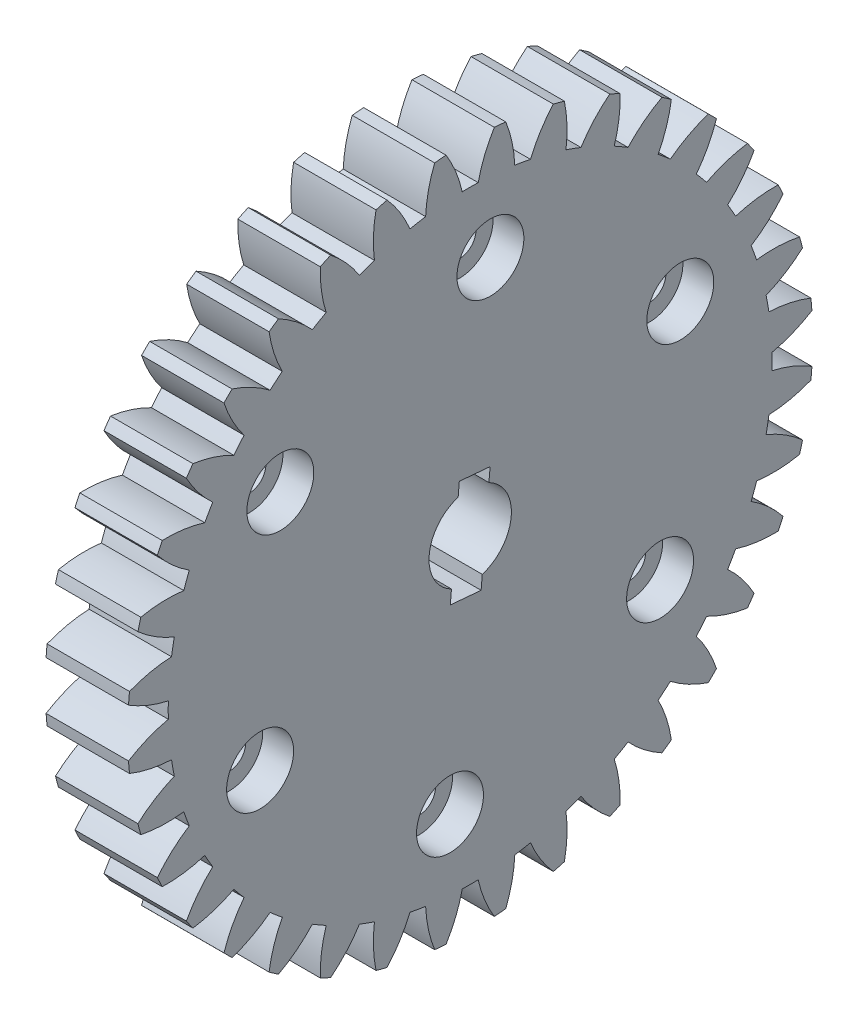
SolidWorks part; units mm, degrees
material "PLA personnalisé"
ref_plane "Plane1" through (0, 0, 0) normal (0, 0, 1) x (1, 0, 0)
ref_plane "Plane2" through (0, 0, 0) normal (0, 1, 0) x (1, 0, 0)
ref_plane "Plane3" through (0, 0, 0) normal (1, 0, 0) x (0, 0, -1)
other "Configuration Table"
sketch "HoldingSke" plane through (0, 0, 0) normal (0, 1, 0) x (1, 0, 0)
  line L0 (0, 0) -> (0.4623, -0.3359)
  line L1 (-15, 0) -> (100, 0) construction
  line L2 (0, 0) -> (-2.1039, 2.3779)
  line L3 (0, 0) -> (-11.863, 4.5341)
  line L4 (0, 0) -> (6.9867, 5.0761)
  line L5 (0, 0) -> (-46.8476, -17.4728)
  line L6 (0, 0) -> (-6.6317, -4.4744)
  line L7 (-2.1039, 2.3779) -> (8.6586, 51.2059)
  line L8 (-76.2, 54.61) -> (-74.8, 54.61)
  line L9 (-71.009, 38.7566) -> (-53.1078, 45.2721)
  line L10 (-76.2, 71.12) -> (104.1128, 71.12)
  line L11 (0, 0) -> (-8, 0)
  line L12 (-76.2, 101.6) -> (-76.147, 101.6)
  line L13 (24.9733, 27.94) -> (52.9518, 28.4284)
  line L14 (24.9733, 27.94) -> (24.9743, 27.94)
  line L15 (24.9733, 27.94) -> (100.4006, 29.5858)
  line L16 (-63.627, -1.75) -> (-12.827, -1.75)
  circle A0 centre (0, 0) radius 4
  circle A1 centre (0, 0) radius 29.3115
  circle A2 centre (0, 0) radius 37.5
  circle A3 centre (0, 0) radius 4
  dimension "MHD" = 58.623
  dimension "Hub_dia" = 75
  dimension "Bore" = 8
  dimension "MBD" = 8
  dimension "Num_teeth" = 36
  dimension "Pitch" = 0.5714
  dimension "Overall_len" = 50
  dimension "Show_teeth" = 36
  dimension "Thickness" = 8
  dimension "OAL" = 50.0001
  dimension "T_dim" = 1.4
  dimension "Ap" = 20
  dimension "H" = 19.05
  dimension "Pitch_radius" = 180.3128
  dimension "Width" = 8
  dimension "Backlash" = 0.053
  dimension "Addendum_fac" = 1
  dimension "Dedendum_fac" = 1.25
  dimension "Clearance_fac" = 0.25
  dimension "Dedendum_add" = 0.001
  dimension "Module" = 1.75
sketch "BasProSke" plane through (0, 0, 0) normal (0, 1, 0) x (1, 0, 0)
  line L0 (-10, 0) -> (60, 0) construction
  line L1 (0, 0) -> (0, 33.25)
  line L2 (0, 0) -> (8, 0)
  line L3 (8, 0) -> (8, 33.25)
  line L4 (8, 33.25) -> (0, 33.25)
  dimension "Thickness" = 8
  dimension "Diameter" = 66.5
revolve "Base-Revolve" add sketch "BasProSke" angle 360 about L0
sketch "TooCutSke" plane through (0, 0, 0) normal (1, 0, 0) x (0, 0, -1)
  line L1 (0, 0) -> (0, 107) construction
  line L2 (0, 0) -> (-1.4667, 31.4658) construction
  line L3 (0, 0) -> (-5.4863, 62.7083) construction
  line L4 (-1.4667, 31.4658) -> (-2.7431, 31.3542) construction
  arc A0 (0.7738, 29.3013) -> (-0.7738, 29.3013) centre (0, 0) ccw
  arc A1 (2.3593, 33.1917) -> (-2.3593, 33.1917) centre (0, 0) ccw
  circle A2 centre (0, 0) radius 31.5 construction
  circle A3 centre (0, 0) radius 29.6003 construction
  arc A4 (-0.7738, 29.3013) -> (-2.3593, 33.1917) centre (-13.0715, 26.5578) ccw
  arc A5 (2.3593, 33.1917) -> (0.7738, 29.3013) centre (13.0715, 26.5578) ccw
  dimension "Root_dia" = 58.623
  dimension "Overcut_dia" = 66.5508
  dimension "Pitch_dia" = 63
  dimension "Base_dia" = 59.2006
  dimension "Flank_rad" = 12.6
  dimension "Half_ang" = 5
  dimension "Half_CT" = 1.2813
extrude "ToothCut" cut sketch "TooCutSke" along normal through all
fillet "Breaks" [suppressed] radius 0.035 tangent propagation no
fillet "RootFillets" [suppressed] radius 0.4385
pattern_circular "TeethCuts" count 36 every 10 about axis through (-10, 0, 0) along (1, 0, 0) of "ToothCut", "RootFillets", "Breaks"
sketch "HubNeaOneSke" plane through (0, 0, 0) normal (-1, 0, 0) x (0, 0, 1)
  circle A0 centre (0, 0) radius 29.3115
  dimension "Diameter" = 58.623
extrude "HubNearOne" [suppressed] add sketch "HubNeaOneSke" along normal blind 42.0001
sketch "HubNeaBotSke" plane through (0, 0, 0) normal (-1, 0, 0) x (0, 0, 1)
  circle A0 centre (0, 0) radius 29.3115
  dimension "Diameter" = 58.623
extrude "HubNearBoth" [suppressed] add sketch "HubNeaBotSke" along normal blind 21
ref_plane "FarPln" through (8, 0, 0) normal (1, 0, 0) x (0, 0, -1)
sketch "HubFarSke" plane through (8, 0, 0) normal (1, 0, 0) x (0, 0, -1)
  circle A0 centre (0, 0) radius 29.3115
  dimension "Diameter" = 58.623
extrude "HubFar" [suppressed] add sketch "HubFarSke" along normal blind 21
sketch "BorSke" plane through (0, 0, 0) normal (1, 0, 0) x (0, 0, -1)
  circle A0 centre (0, 0) radius 4
  dimension "Diameter" = 8
extrude "Bore" cut sketch "BorSke" along normal mid plane 100.0001
sketch "KeySke" plane through (0, 0, 0) normal (1, 0, 0) x (0, 0, -1)
  line L0 (-1.5, 0) -> (-1.5, 5.4)
  line L1 (-1.5, 5.4) -> (1.5, 5.4)
  line L2 (1.5, 5.4) -> (1.5, 0)
  line L3 (0, 0) -> (0, 34) construction
  line L4 (-1.5, 0) -> (1.5, 0)
  dimension "Offset" = 5.4
  dimension "Width" = 3
extrude "Keyway" [suppressed] cut sketch "KeySke" along normal mid plane 100.0001
pattern_circular "Keyway2" [suppressed] count 2 every 90 about axis through (-10, 0, 0) along (1, 0, 0) reverse direction yes
sketch "Esquisse2" plane through (8, 0, 0) normal (1, 0, 0) x (0, 0, -1)
  line L0 (2.8979, 33.1235) -> (0, 0) construction
  line L1 (1.3673, 15.6288) -> (2.5547, 29.2)
  arc A0 (3.4508, 33.0704) -> (2.3442, 33.1673) centre (0, 0) ccw construction
  circle A1 centre (0, 0) radius 29.3115
  circle A2 centre (0, 0) radius 15.6885
  circle A3 centre (1.961, 22.4144) radius 1.6
  circle A4 centre (0, 0) radius 22.5
  dimension "D1" = 3.2
  dimension "D2" = 45
extrude "Enlèv. mat.-Extru.2" cut sketch "Esquisse2" against normal blind 10 contours A3
sketch "Esquisse3" plane through (8, 0, 0) normal (1, 0, 0) x (0, 0, -1)
  circle A0 centre (1.961, 22.4144) radius 3.25
  dimension "D1" = 6.5
extrude "Enlèv. mat.-Extru.3" cut sketch "Esquisse3" against normal blind 3
pattern_circular "Répétition circulaire1" count 6 over 360 about axis through (50.0001, 0, 0) along (-1, 0, 0) of "Enlèv. mat.-Extru.2", "Enlèv. mat.-Extru.3"
sketch "Esquisse4" plane through (8, 0, 0) normal (1, 0, 0) x (0, 0, -1)
  line L0 (0, 0) -> (1.961, 22.4144) construction
  line L1 (1.0585, -5.1117) -> (-1.9301, -4.8502)
  line L2 (1.0585, -5.1117) -> (1.9301, 4.8502)
  line L3 (1.9301, 4.8502) -> (-1.0585, 5.1117)
  line L4 (-1.9301, -4.8502) -> (-1.0585, 5.1117)
  line L5 (1.0585, -5.1117) -> (-1.0585, 5.1117) construction
  line L6 (1.9301, 4.8502) -> (-1.9301, -4.8502) construction
  point P0 (0, 0)
  dimension "D1" = 10
  dimension "D2" = 3
extrude "Enlèv. mat.-Extru.4" cut sketch "Esquisse4" against normal blind 10
equation "' \"Module@HoldingSke\" = 6.35"
equation "' \"Num_teeth@HoldingSke\" = 12"
equation "' \"Ap@HoldingSke\" =  20"
equation "' \"Ap@HoldingSke\" = 20"
equation "' \"Width@HoldingSke\" = 0.5 * 25.4"
equation "' \"Hub_dia@HoldingSke\"= 1 * 25.4"
equation "' \"Hub_dia@HoldingSke\" = 1 * 25.4"
equation "' \"Overall_len@HoldingSke\" = 1.0 * 25.4"
equation "' \"Bore@HoldingSke\" = 0.75 * 25.4"
equation "' \"T_dim@HoldingSke\" = 0.1 * 25.4"
equation "' \"Width@KeySke\" = 0.25 * 25.4"
equation "' \"Show_teeth@HoldingSke\" = 13"
equation "' \"Backlash@HoldingSke\" = 0.009 * 25.4"
equation "' \"Addendum_fac@HoldingSke\" = 1.0"
equation "' \"Dedendum_fac@HoldingSke\" = 1.25"
equation "' \"Dedendum_add@HoldingSke\" = 0.00005 * 25.4"
equation "' \"Clearance_fac@HoldingSke\" = 0.25"
equation "\"Pitch@HoldingSke\" = 1 / \"Module@HoldingSke\""
equation "\"Overcut_dia@TooCutSke\" = (\"Num_teeth@HoldingSke\" + 2 * \"Addendum_fac@HoldingSke\") / \"Pitch@HoldingSke\" + 0.002 * 25.4"
equation "\"Pitch_dia@TooCutSke\" = \"Num_teeth@HoldingSke\" / \"Pitch@HoldingSke\""
equation "\"Base_dia@TooCutSke\" = \"Num_teeth@HoldingSke\" / \"Pitch@HoldingSke\" * cos((\"Ap@HoldingSke\"  * 3.14159265 / 180))"
equation "\"Root_dia@TooCutSke\" = (\"Num_teeth@HoldingSke\" + 2) / \"Pitch@HoldingSke\" - 2 * (\"Addendum_fac@HoldingSke\" + \"Dedendum_fac@HoldingSke\") / \"Pitch@HoldingSke\" - \"Dedendum_add@HoldingSke\" * 2"
equation "\"Half_ang@TooCutSke\" = 180 / \"Num_teeth@HoldingSke\""
equation "\"Half_CT@TooCutSke\" = \"Num_teeth@HoldingSke\" / \"Pitch@HoldingSke\" * sin((3.14159265 / 2 / \"Num_teeth@HoldingSke\")) / 2 - 7 * \"Backlash@HoldingSke\" / 4"
equation "\"Flank_rad@TooCutSke\" = \"Num_teeth@HoldingSke\" / \"Pitch@HoldingSke\" / 5"
equation "\"Radius@RootFillets\" = \"Clearance_fac@HoldingSke\" / \"Pitch@HoldingSke\" + \"Dedendum_add@HoldingSke\""
equation "\"Break_rad@Breaks\" = 0.02 / \"Pitch@HoldingSke\""
equation "\"Thickness@HoldingSke\" = \"Width@HoldingSke\""
equation "\"OAL@HoldingSke\" = \"Thickness@HoldingSke\""
equation "\"MHD@HoldingSke\" = (\"Num_teeth@HoldingSke\" + 2) / \"Pitch@HoldingSke\" - 2 * (\"Addendum_fac@HoldingSke\" + \"Dedendum_fac@HoldingSke\")  / \"Pitch@HoldingSke\" - \"Dedendum_add@HoldingSke\" * 2"
equation "\"MBD@HoldingSke\" = (\"Num_teeth@HoldingSke\" + 2) / \"Pitch@HoldingSke\" - 2 * (\"Addendum_fac@HoldingSke\" + \"Dedendum_fac@HoldingSke\")  / \"Pitch@HoldingSke\" - \"Dedendum_add@HoldingSke\" * 2 - 0.002 * 25.4"
equation "\"MHD@HoldingSke\" = ((sgn( \"MHD@HoldingSke\" - \"Hub_dia@HoldingSke\" )-1)*( \"MHD@HoldingSke\" - \"Hub_dia@HoldingSke\" ))/-2+ \"Hub_dia@HoldingSke\""
equation "\"MBD@HoldingSke\" = ((sgn( \"MBD@HoldingSke\" - \"Bore@HoldingSke\" )-1)*( \"MBD@HoldingSke\" - \"Bore@HoldingSke\" ))/-2+ \"Bore@HoldingSke\""
equation "\"OAL@HoldingSke\" = ((sgn( \"OAL@HoldingSke\" - \"Overall_len@HoldingSke\" )+1)*( \"OAL@HoldingSke\" - \"Overall_len@HoldingSke\" ))/2 + \"Overall_len@HoldingSke\" + 0.000002 * 25.4"
equation "\"Num_teeth@TeethCuts\" = int( \"Show_teeth@HoldingSke\" ) + 1"
equation "\"Num_teeth@TeethCuts\" = ((sgn( \"Num_teeth@TeethCuts\" - \"Num_teeth@HoldingSke\" )-1)*( \"Num_teeth@TeethCuts\" - \"Num_teeth@HoldingSke\" ))/-2+ \"Num_teeth@HoldingSke\""
equation "\"Num_teeth@TeethCuts\" = ((sgn( \"Num_teeth@TeethCuts\" - 2.0)+1)*( \"Num_teeth@TeethCuts\" - 2.0))/2 +2.0"
equation "\"Angle@TeethCuts\" = 360.0 / \"Num_teeth@HoldingSke\""
equation "\"Diameter@BasProSke\" = (\"Num_teeth@HoldingSke\" + 2 * \"Addendum_fac@HoldingSke\") / \"Pitch@HoldingSke\""
equation "\"Thickness@BasProSke\"  = \"Thickness@HoldingSke\""
equation "' \"Fillet_rad@BasProSke\" =  \"Thickness@HoldingSke\" * 0.05"
equation "' \"Fillet_rad@BasProSke\" = \"Thickness@HoldingSke\" * 0.05"
equation "\"MHD@HoldingSke\" = ((sgn( \"MHD@HoldingSke\" - \"Root_dia@TooCutSke\" )-1)*( \"MHD@HoldingSke\" - \"Root_dia@TooCutSke\" ))/-2+ \"Root_dia@TooCutSke\""
equation "\"Diameter@HubNeaOneSke\" = \"MHD@HoldingSke\""
equation "\"Length@HubNearOne\" = \"OAL@HoldingSke\" - \"Thickness@BasProSke\""
equation "\"Diameter@HubNeaBotSke\" = \"MHD@HoldingSke\""
equation "\"Length@HubNearBoth\" = ( \"OAL@HoldingSke\" - \"Thickness@BasProSke\" ) / 2.0"
equation "\"Thickness@FarPln\" = \"Thickness@BasProSke\""
equation "\"Diameter@HubFarSke\" = \"MHD@HoldingSke\""
equation "\"Length@HubFar\" = ( \"OAL@HoldingSke\" - \"Thickness@BasProSke\" ) / 2.0"
equation "\"Diameter@BorSke\" = \"MBD@HoldingSke\""
equation "\"D1@Bore\" = \"OAL@HoldingSke\" * 2.0"
equation "\"D1@Keyway\" = \"OAL@HoldingSke\" * 2.0"
equation "\"Offset@KeySke\" = \"T_dim@HoldingSke\" + \"MBD@HoldingSke\" / 2.0"
